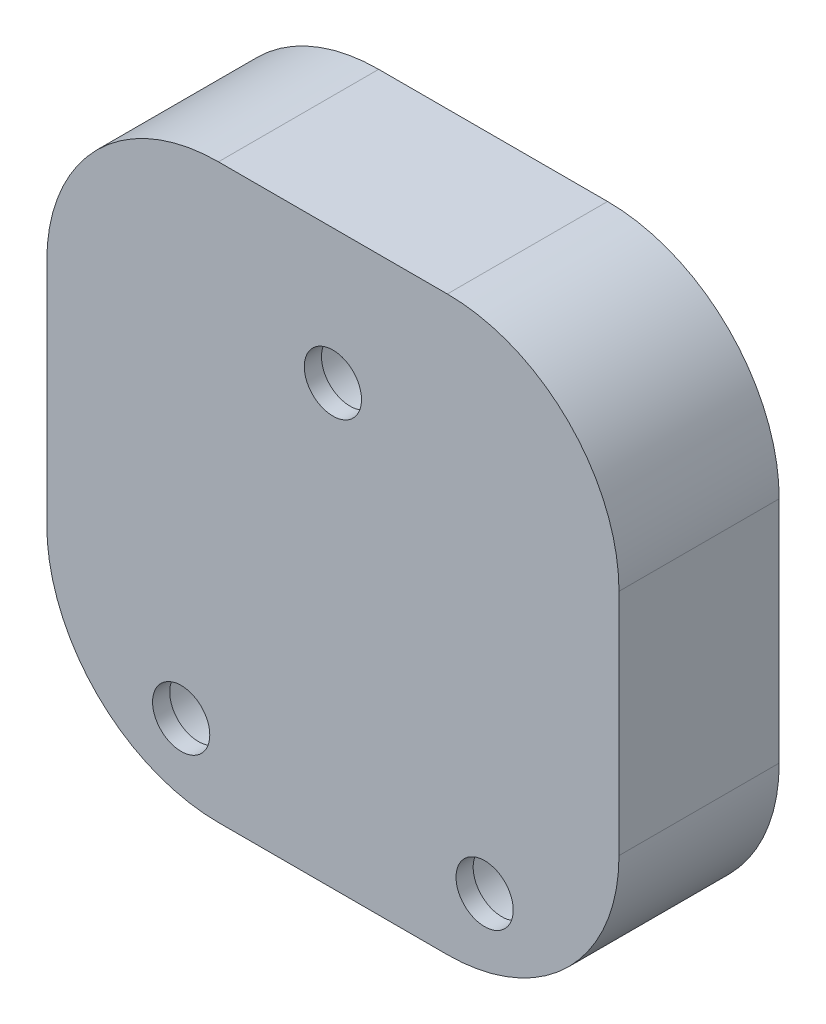
SolidWorks part; units mm, degrees
ref_plane "Front Plane" through (0, 0, 0) normal (0, 0, 1) x (1, 0, 0)
ref_plane "Top Plane" through (0, 0, 0) normal (0, 1, 0) x (1, 0, 0)
ref_plane "Right Plane" through (0, 0, 0) normal (1, 0, 0) x (0, 0, -1)
sketch "Sketch1" plane through (0, 0, 0) normal (0, 0, 1) x (1, 0, 0)
  line L0 (0, 64.0165) -> (0, 0) construction
  line L6 (-50, 87.5) -> (50, 87.5)
  line L7 (-50, 87.5) -> (-50, -12.5)
  line L8 (-50, -12.5) -> (50, -12.5)
  line L9 (50, 87.5) -> (50, -12.5)
  circle A0 centre (0, 0) radius 4.025
  circle A1 centre (26.5165, 64.0165) radius 4.025
  circle A2 centre (-26.5165, 64.0165) radius 4.025
  circle A3 centre (0, 64.0165) radius 8.1
  circle A4 centre (-26.5165, 0) radius 8.1
  circle A5 centre (26.5165, 0) radius 8.1
  point P4 (0, -12.5)
  point P10 (-50, 37.5)
  dimension "D3" = 8.05
  dimension "D4" = 16.2
  dimension "D5" = 16.2
  dimension "D6" = 16.2
  dimension "D1" = 100
  dimension "D2" = 100
extrude "Boss-Extrude1" add sketch "Sketch1" against normal blind 25
sketch "Sketch2" plane through (0, 0, 0) normal (0, 0, 1) x (1, 0, 0)
  line L4 (-50, 87.5) -> (-50, -12.5)
  line L5 (-50, -12.5) -> (50, -12.5)
  line L6 (50, -12.5) -> (50, 87.5)
  line L7 (50, 87.5) -> (-50, 87.5)
  line L8 (-50, 87.5) -> (-50, -12.5)
  line L9 (-50, -12.5) -> (50, -12.5)
  line L10 (50, -12.5) -> (50, 87.5)
  line L11 (50, 87.5) -> (-50, 87.5)
  circle A0 centre (0, 64.0165) radius 5
  circle A1 centre (26.5165, 0) radius 5
  circle A2 centre (-26.5165, 0) radius 5
  dimension "D2" = 10
  dimension "D3" = 10
  dimension "D4" = 10
  dimension "D1" = 0
extrude "Boss-Extrude2" add sketch "Sketch2" along normal blind 3
fillet "Fillet1" radius 30 4 edges at (50, 87.5, -11) (-50, 87.5, -11) (50, -12.5, -11) (-50, -12.5, -11)
fillet "Fillet2" radius 3 3 edges at (34.6165, 0, -25) (-18.4165, 0, -25) (8.1, 64.0165, -25)
sketch "Sketch3" plane through (0, 0, -25) normal (0, 0, -1) x (-1, 0, 0)
  circle A0 centre (0, 37.5) radius 7.5
  dimension "D1" = 15
extrude "Cut-Extrude1" cut sketch "Sketch3" against normal offset from surface (25 mm away) 3 up to face at (31.5165, 0, 3)
fillet "Fillet3" radius 3 1 edges at (-7.5, 37.5, -25)
